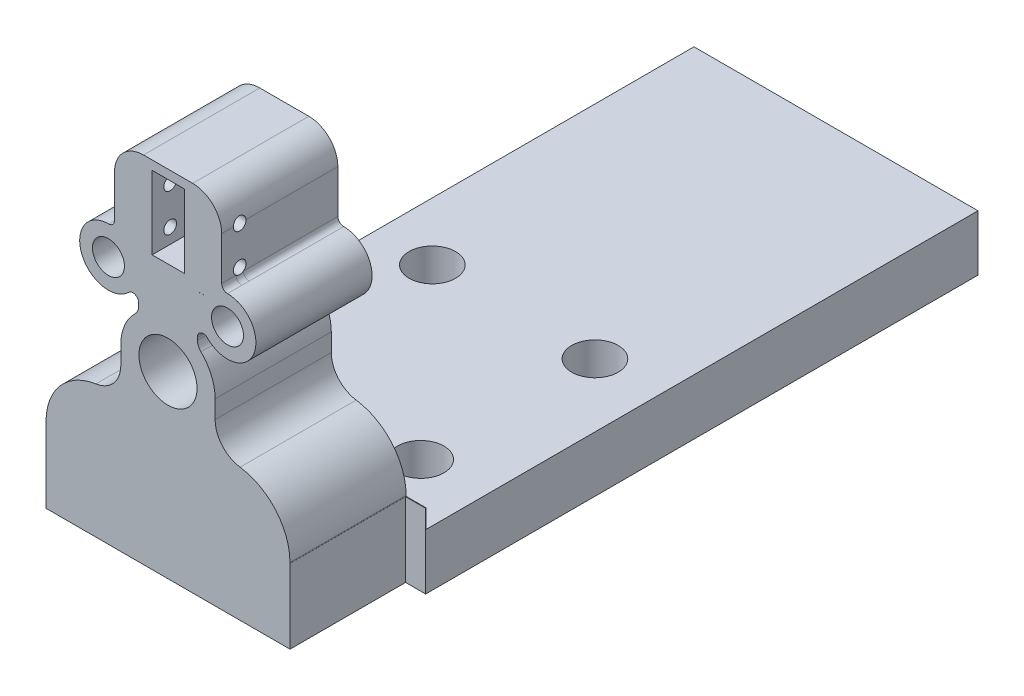
SolidWorks part; units mm, degrees
ref_plane "Alzado" through (0, 0, 0) normal (0, 0, 1) x (1, 0, 0)
ref_plane "Planta" through (0, 0, 0) normal (0, 1, 0) x (1, 0, 0)
ref_plane "Vista lateral" through (0, 0, 0) normal (1, 0, 0) x (0, 0, -1)
sketch "Croquis1" plane through (0, 0, 0) normal (0, 0, 1) x (1, 0, 0)
  line L0 (-5.0668, -5.1496) -> (-5.0668, -8.1496)
  line L1 (5.0477, -8.1756) -> (5.0477, -5.1756)
  line L2 (-8.1437, -14.5125) -> (8.0918, -14.5125) construction
  line L3 (-5.0668, -5.1496) -> (-6.0668, -5.1496)
  line L4 (-6.0259, 0) -> (-5.0259, 0)
  line L5 (6.0937, -0.0171) -> (5.0259, 0)
  line L6 (5.0477, -5.1756) -> (6.0477, -5.1756)
  line L7 (-5.0259, 0) -> (5.0259, 0)
  line L12 (-0.0259, -14.5125) -> (-0.0259, 3.7196) construction
  line L13 (10.2241, -2.6334) -> (-0.0259, -14.5125) construction
  line L14 (-0.0259, -14.5125) -> (-10.276, -2.5412) construction
  line L15 (-10.276, -2.5412) -> (-0.0259, -2.5412) construction
  line L16 (-0.0259, -2.5412) -> (10.2241, -2.6334) construction
  arc A0 (-5.0668, -8.1496) -> (5.0477, -8.1756) centre (-0.0259, -14.5125) ccw
  circle A1 centre (-0.0259, -14.5125) radius 5
  arc A2 (-6.0259, 0) -> (-6.0668, -5.1496) centre (-10.276, -2.5412) ccw
  circle A3 centre (-10.276, -2.5412) radius 2.75
  arc A4 (6.0937, -0.0171) -> (6.0477, -5.1756) centre (10.2241, -2.6334) cw
  circle A5 centre (10.2241, -2.6334) radius 2.75
  point P18 (0, 0)
  dimension "D1" = 10.2501
  dimension "D5" = 5.5
  dimension "D3" = 3
  dimension "D4" = 1
  dimension "D7" = 10.25
  dimension "D8" = 15.69
  dimension "D10" = 15.76
extrude "Saliente-Extruir1" add sketch "Croquis1" along normal blind 20
ref_plane "Plano1" through (0, 0, 10) normal (0, 0, -1) x (-1, 0, 0)
sketch "Croquis5" plane through (0, 0, 10) normal (0, 0, -1) x (-1, 0, 0)
  line L0 (0.0259, -14.5125) -> (0.0259, -32.5925) construction
  line L1 (-8.0918, -14.5125) -> (-8.0918, -32.5925)
  line L2 (-8.0918, -32.5925) -> (8.1437, -32.5925)
  line L3 (8.1437, -32.5925) -> (8.1437, -14.5125)
  arc A0 (-5.0477, -8.1756) -> (5.0668, -8.1496) centre (0.0259, -14.5125) ccw construction
  arc A1 (8.1437, -14.5125) -> (-8.0918, -14.5125) centre (0.0259, -14.5125) cw
  dimension "D1" = 18.08
extrude "Saliente-Extruir4" add sketch "Croquis5" along normal mid plane 20
sketch "Croquis7" plane through (0, 0, 20) normal (0, 0, 1) x (1, 0, 0)
  line L0 (20.9741, -32.5925) -> (-21.0259, -32.5925)
  line L2 (8.0918, -32.5925) -> (-8.1437, -32.5925) construction
  point P3 (-0.0259, -32.5925)
  point P6 (-0.0259, -32.5925)
  dimension "D1" = 42
extrude "Extruir-Lámina1" add sketch "Croquis7" against normal blind 20 thin
sketch "Croquis8" plane through (0, 0, 20) normal (0, 0, 1) x (1, 0, 0)
  line L0 (-0.0259, -14.5125) -> (-0.0259, -32.5925) construction
  line L5 (20.9741, -32.5925) -> (-21.0259, -32.5925) construction
  line L7 (-21.0259, -32.5925) -> (20.9855, -32.5925)
  line L8 (-21.0259, -32.5925) -> (-21.0259, -45.386)
  line L9 (-21.0259, -45.386) -> (20.9855, -45.386)
  line L10 (20.9855, -32.5925) -> (20.9855, -45.386)
extrude "Saliente-Extruir6" add sketch "Croquis8" against normal blind 52
fillet "Redondeo1" radius 2 4 edges at (-5.0668, -8.1496, 10) (5.0477, -8.1756, 10) (-5.0668, -5.1496, 10) (5.0477, -5.1756, 10)
fillet "Redondeo2" radius 1 2 edges at (6.0477, -5.1756, 10) (-6.0668, -5.1496, 10)
sketch "Croquis9" plane through (0, 0, 20) normal (0, 0, 1) x (1, 0, 0)
  line L1 (9.2249, 0) -> (-9.2249, 0)
  line L2 (9.2249, 0) -> (9.2249, 15.7)
  line L3 (9.2249, 15.7) -> (-9.2249, 15.7)
  line L4 (-9.2249, 0) -> (-9.2249, 15.7)
  line L5 (-9.2249, 0) -> (6.0259, 0) construction
  line L6 (0, 1.55) -> (-0.0202, -45.386) construction
  line L7 (-2.75, 14.15) -> (2.85, 14.15)
  line L8 (-2.75, 14.15) -> (-2.75, 1.55)
  line L9 (-2.75, 1.55) -> (2.85, 1.55)
  line L10 (2.85, 14.15) -> (2.85, 1.55)
  line L11 (-21.0259, -45.386) -> (20.9855, -45.386) construction
  circle A0 centre (-10.276, -2.5412) radius 2.75 construction
  point P3 (0, 0)
  point P4 (-8.9189, -0.1494)
  point P10 (0, 0)
  point P20 (0, 0)
  point P21 (0, 0)
  dimension "D1" = 15.7
  dimension "D2" = 1.55
  dimension "D3" = 12.6
  dimension "D4" = 5.6
  dimension "D5" = 6.3749
extrude "Saliente-Extruir7" add sketch "Croquis9" against normal up to vertex (13.6 mm away)
sketch "Croquis11" plane through (9.2249, 0, 0) normal (1, 0, 0) x (0, 0, -1)
  line L0 (0, 14.15) -> (-20, 14.15) construction
  circle A0 centre (-16.8993, 10.65) radius 1.1
  circle A1 centre (-16.8993, 4.15) radius 1.1
  dimension "D1" = 6.5
  dimension "D2" = 2.2
  dimension "D3" = 2.2
  dimension "D4" = 3.5
extrude "Cortar-Extruir1" cut sketch "Croquis11" against normal through all both and the other way through all
fillet "Redondeo4" radius 5 2 edges at (8.0918, -22.5925, 10) (-8.1437, -22.5925, 10)
fillet "Redondeo5" radius 10 8 edges at (17.033, -22.5925, 0) (13.0918, -22.5925, 10) (17.033, -22.5925, 20) (20.9741, -22.5925, 10) (-17.0848, -22.5925, 20) (-13.1437, -22.5925, 10) (-17.0848, -22.5925, 0) (-21.0259, -22.5925, 10)
sketch "Croquis12" plane through (0, -32.5925, 0) normal (0, 1, 0) x (1, 0, 0)
  line L0 (0, 0) -> (-0.0202, 32) construction
  line L1 (24.4399, -0.1) -> (-24.4601, -0.1)
  line L2 (24.4399, -0.1) -> (24.4399, 32.1)
  line L3 (24.4399, 32.1) -> (-24.4601, 32.1)
  line L4 (-24.4601, -0.1) -> (-24.4601, 32.1)
  line L5 (24.4399, -0.1) -> (-24.4601, 32.1) construction
  line L6 (24.4399, 32.1) -> (-24.4601, -0.1) construction
  line L7 (20.9855, 32) -> (-21.0259, 32) construction
  point P0 (-0.0101, 16)
  point P11 (-0.0101, 16)
  dimension "D1" = 48.9
  dimension "D2" = 32.2
extrude "Saliente-Extruir8" add sketch "Croquis12" against normal up to surface (12.7935 mm away) up to face at (-0.0202, -45.386, -6)
sketch "Croquis13" plane through (0, 0, -32.1) normal (0, 0, -1) x (-1, 0, 0)
  line L1 (-24.4399, -32.5925) -> (24.4601, -32.5925)
  line L2 (-24.4399, -32.5925) -> (-24.4399, -45.386)
  line L3 (-24.4399, -45.386) -> (24.4601, -45.386)
  line L4 (24.4601, -32.5925) -> (24.4601, -45.386)
extrude "Saliente-Extruir9" add sketch "Croquis13" along normal blind 17.85
sketch "Croquis14" plane through (0, -32.5925, 0) normal (0, 1, 0) x (1, 0, 0)
  line L0 (-24.4601, 49.95) -> (24.4399, 49.95) construction
  line L1 (-24.4601, 49.95) -> (-24.4601, -0.1) construction
  circle A0 centre (-14.4601, 39.95) radius 4
  circle A1 centre (13.5399, 39.95) radius 4
  circle A2 centre (13.5399, 9.95) radius 4
  circle A3 centre (-14.4601, 9.95) radius 4
  dimension "D1" = 8
  dimension "D2" = 10
  dimension "D3" = 10
  dimension "D4" = 2
  dimension "D5" = 2
extrude "Cortar-Extruir2" cut sketch "Croquis14" against normal blind 17.85
fillet "Redondeo6" radius 1 2 edges at (9.2249, 2.1527, 10) (-9.2249, 2.2978, 10)
fillet "Redondeo7" radius 5 2 edges at (-9.2249, 15.7, 10) (9.2249, 15.7, 10)
sketch "Croquis16" plane through (0, 0, 20) normal (0, 0, 1) x (1, 0, 0)
  point P6 (0, 0)
sketch "Croquis17" plane through (24.4399, 0, 0) normal (1, 0, 0) x (0, 0, -1)
  line L0 (-0.1, -45.386) -> (95, -45.386) construction
  line L1 (95, -45.386) -> (95, -35.786) construction
  line L4 (95, -35.786) -> (0, -35.786)
  line L5 (95, -35.786) -> (95, -22.5424)
  line L6 (95, -22.5424) -> (0, -22.5424)
  line L7 (0, -35.786) -> (0, -22.5424)
  dimension "D1" = 95.1
  dimension "D2" = 9.6
extrude "Cortar-Extruir10" cut sketch "Croquis17" against normal through all
sketch "Croquis18" plane through (24.4399, 0, 0) normal (1, 0, 0) x (0, 0, -1)
  line L0 (-0.1, -45.386) -> (-0.1, -35.786) construction
  line L1 (-0.1, -32.5925) -> (-0.1, -45.386) construction
  line L2 (-0.1, -35.786) -> (95, -35.786) construction
  line L3 (95, -35.786) -> (95, -45.386) construction
  line L12 (95, -45.386) -> (-0.1, -45.386) construction
  line L14 (95, -35.786) -> (49.95, -35.786)
  line L15 (95, -35.786) -> (95, -45.386)
  line L16 (95, -45.386) -> (49.95, -45.386)
  line L17 (49.95, -35.786) -> (49.95, -45.386)
  dimension "D1" = 9.6
  dimension "D2" = 95.1
sketch "Croquis19" plane through (24.4399, 0, 0) normal (1, 0, 0) x (0, 0, -1)
extrude "Saliente-Extruir11" add sketch "Croquis18" against normal up to surface (48.9 mm away) up to face at (-24.4601, -37.9215, -16.6167)
